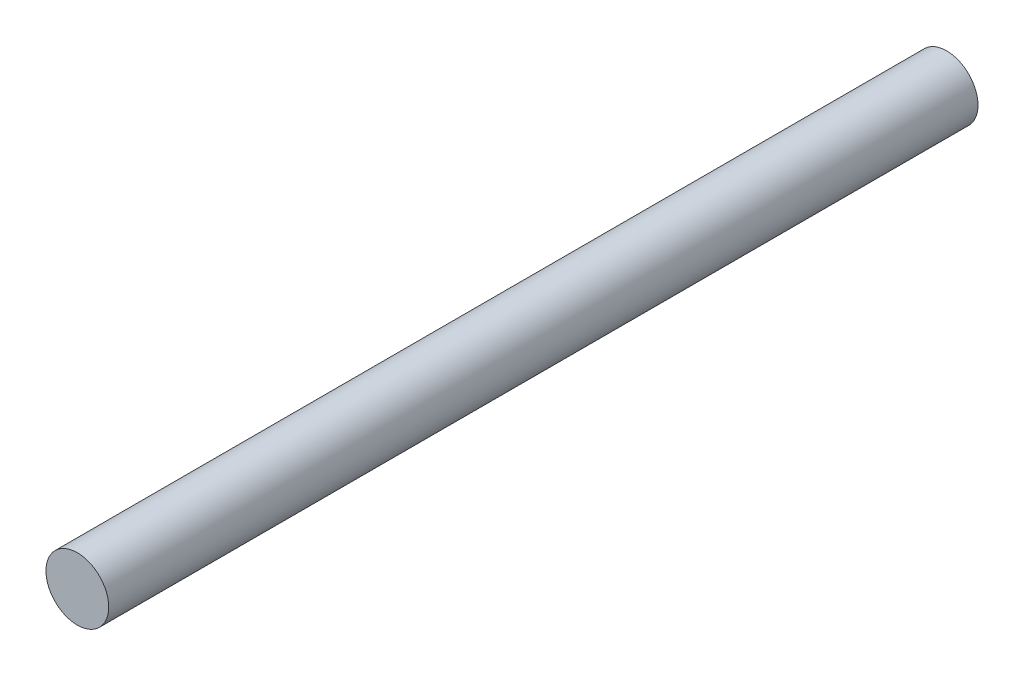
SolidWorks part; units mm, degrees
ref_plane "Front Plane" through (0, 0, 0) normal (0, 0, 1) x (1, 0, 0)
ref_plane "Top Plane" through (0, 0, 0) normal (0, 1, 0) x (1, 0, 0)
ref_plane "Right Plane" through (0, 0, 0) normal (1, 0, 0) x (0, 0, -1)
sketch "Sketch2" plane through (0, 0, 0) normal (0, 0, 1) x (1, 0, 0)
  circle A0 centre (0, 0) radius 1.985
  dimension "D1" = 3.97
extrude "Boss-Extrude1" add sketch "Sketch2" along normal blind 55
